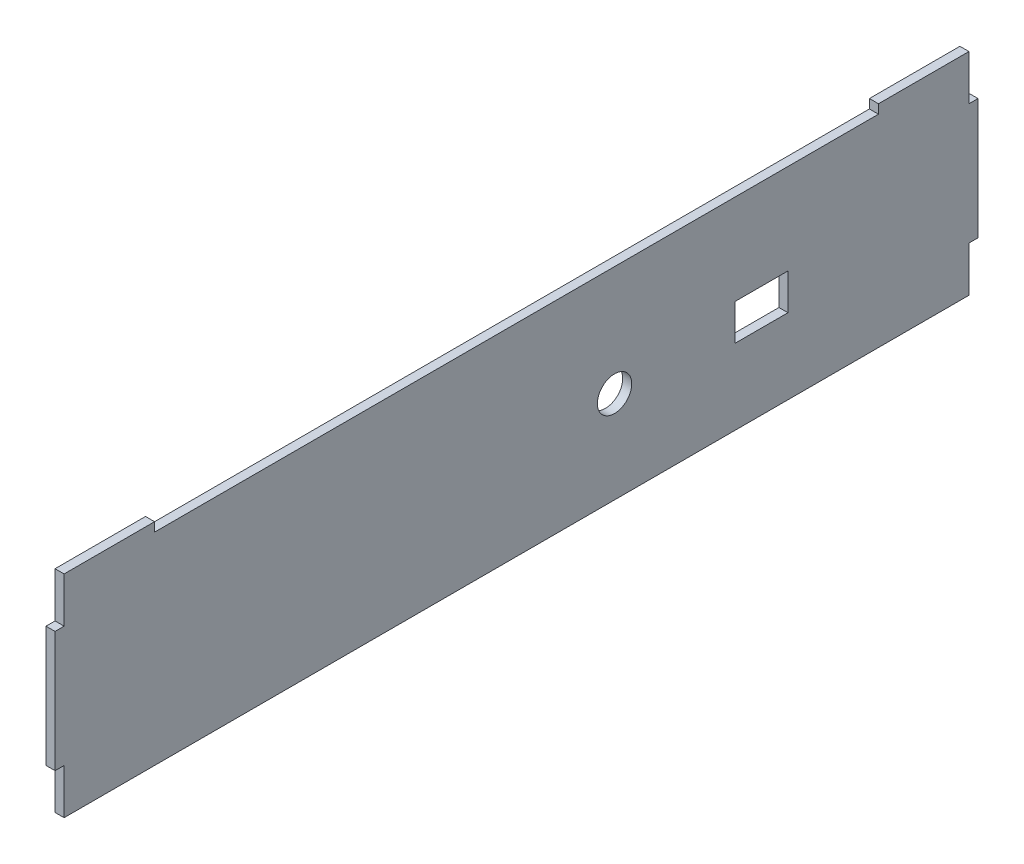
SolidWorks part; units mm, degrees
ref_plane "Front Plane" through (0, 0, 0) normal (0, 0, 1) x (1, 0, 0)
ref_plane "Top Plane" through (0, 0, 0) normal (0, 1, 0) x (1, 0, 0)
ref_plane "Right Plane" through (0, 0, 0) normal (1, 0, 0) x (0, 0, -1)
sketch "Sketch1" plane through (0, 0, 0) normal (1, 0, 0) x (0, 0, -1)
  line L0 (18.8554, 70) -> (318.8554, 70)
  line L1 (318.8554, 70) -> (318.8554, 55)
  line L2 (318.8554, 55) -> (321.8554, 55)
  line L3 (321.8554, 55) -> (321.8554, 15)
  line L4 (321.8554, 15) -> (318.8554, 15)
  line L5 (318.8554, 15) -> (318.8554, 0)
  line L6 (318.8554, 0) -> (18.8554, 0)
  line L7 (18.8554, 0) -> (18.8554, 15)
  line L8 (18.8554, 15) -> (15.8554, 15)
  line L9 (15.8554, 15) -> (15.8554, 55)
  line L10 (15.8554, 55) -> (18.8554, 55)
  line L11 (18.8554, 55) -> (18.8554, 70)
  dimension "D1" = 300
  dimension "D2" = 300
  dimension "D3" = 40
  dimension "D4" = 40
  dimension "D5" = 15
  dimension "D6" = 15
  dimension "D7" = 15
  dimension "D8" = 15
  dimension "D9" = 3
  dimension "D10" = 3
  dimension "D11" = 3
  dimension "D12" = 3
extrude "Boss-Extrude2" add sketch "Sketch1" along normal blind 3
sketch "Sketch3" plane through (3, 0, 0) normal (1, 0, 0) x (0, 0, -1)
  line L0 (48.8554, 70) -> (48.8554, 67)
  line L1 (318.8554, 70) -> (18.8554, 70) construction
  line L2 (48.8554, 67) -> (288.8554, 67)
  line L3 (288.8554, 67) -> (288.8554, 70)
  line L4 (318.8554, 55) -> (318.8554, 70) construction
  dimension "D1" = 240
  dimension "D2" = 3
  dimension "D3" = 30
extrude "Cut-Extrude1" cut sketch "Sketch3" against normal blind 3 and the other way through all
sketch "Sketch4" plane through (3, 0, 0) normal (1, 0, 0) x (0, 0, -1)
  line L0 (318.8554, 0) -> (318.8554, 15) construction
  line L1 (241.3554, 37) -> (258.8554, 37)
  line L2 (241.3554, 37) -> (241.3554, 25)
  line L3 (241.3554, 25) -> (258.8554, 25)
  line L4 (258.8554, 37) -> (258.8554, 25)
  line L5 (18.8554, 0) -> (318.8554, 0) construction
  dimension "D1" = 17.5
  dimension "D2" = 12
  dimension "D3" = 60
  dimension "D4" = 25
extrude "Cut-Extrude2" cut sketch "Sketch4" against normal blind 10
sketch "Sketch5" plane through (3, 0, 0) normal (1, 0, 0) x (0, 0, -1)
  line L0 (241.3554, 37) -> (241.3554, 25) construction
  line L1 (18.8554, 0) -> (318.8554, 0) construction
  circle A0 centre (201.3554, 30.5) radius 5.7
  dimension "D1" = 11.4
  dimension "D2" = 40
  dimension "D3" = 30.5
extrude "Cut-Extrude3" cut sketch "Sketch5" against normal blind 10
